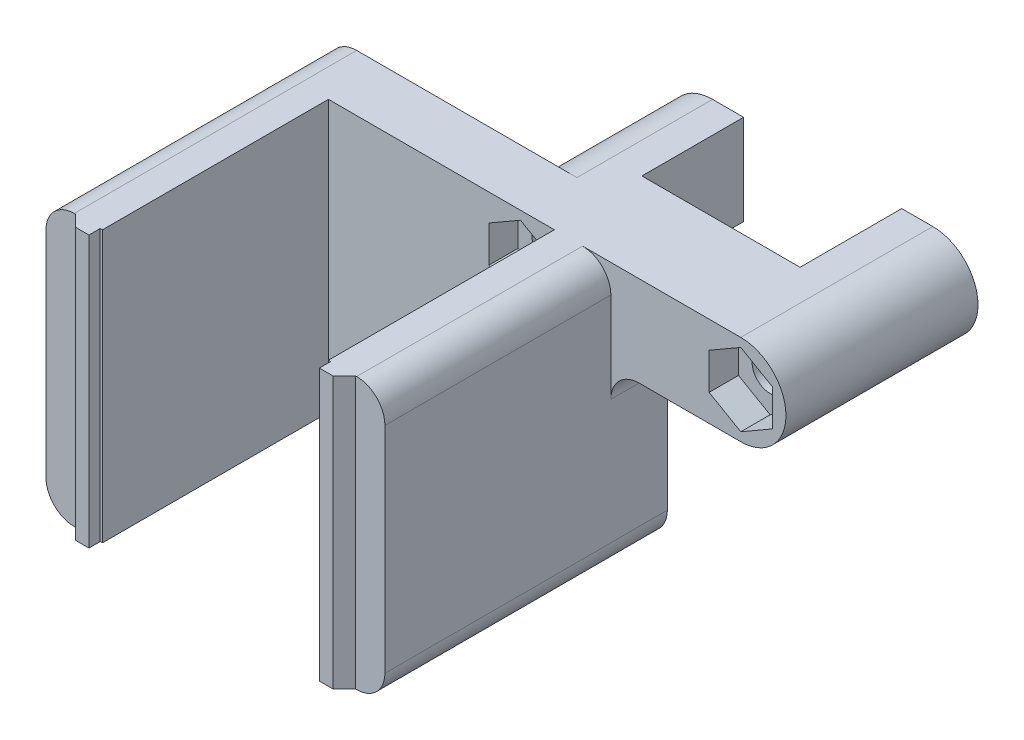
SolidWorks part; units mm, degrees
ref_plane "Спереди" through (0, 0, 0) normal (0, 0, 1) x (1, 0, 0)
ref_plane "Сверху" through (0, 0, 0) normal (0, 1, 0) x (1, 0, 0)
ref_plane "Справа" through (0, 0, 0) normal (1, 0, 0) x (0, 0, -1)
sketch "Эскиз1" plane through (0, 0, 0) normal (0, 0, 1) x (1, 0, 0)
  line L1 (0, 0) -> (30, 0)
  line L2 (0, 0) -> (0, -24)
  line L3 (0, -24) -> (30, -24)
  line L4 (30, 0) -> (30, -24)
  dimension "D1" = 24
  dimension "D2" = 30
extrude "Бобышка-Вытянуть1" add sketch "Эскиз1" along normal blind 5
sketch "Эскиз2" plane through (0, 0, 5) normal (0, 0, 1) x (1, 0, 0)
  line L1 (0, -24) -> (5, -24)
  line L2 (0, -24) -> (0, 0)
  line L3 (0, 0) -> (5, 0)
  line L4 (5, -24) -> (5, 0)
  line L5 (30, 0) -> (0, 0) construction
  line L7 (30, -24) -> (25, -24)
  line L8 (30, -24) -> (30, 0)
  line L9 (30, 0) -> (25, 0)
  line L10 (25, -24) -> (25, 0)
  dimension "D1" = 24
  dimension "D2" = 5
  dimension "D3" = 24
  dimension "D4" = 5
extrude "Бобышка-Вытянуть2" add sketch "Эскиз2" along normal blind 20
sketch "Эскиз3" plane through (0, 0, 0) normal (0, 1, 0) x (1, 0, 0)
  line L0 (25.2, -25) -> (25.2, -26)
  line L1 (30, -25) -> (25, -25) construction
  line L2 (25.2, -26) -> (26.4, -26)
  line L3 (26.4, -26) -> (27.4, -25)
  line L4 (27.4, -25) -> (25.2, -25)
  line L5 (25, -25) -> (25, -5) construction
  line L6 (4.8, -25) -> (4.8, -26)
  line L7 (5, -25) -> (0, -25) construction
  line L8 (4.8, -26) -> (3.6, -26)
  line L9 (3.6, -26) -> (2.6, -25)
  line L10 (2.6, -25) -> (4.8, -25)
  line L11 (5, -25) -> (5, -5) construction
  dimension "D1" = 45
  dimension "D2" = 1
  dimension "D3" = 1.2
  dimension "D4" = 0.2
  dimension "D5" = 45
  dimension "D6" = 0.2
  dimension "D7" = 1.2
  dimension "D8" = 1
extrude "Бобышка-Вытянуть3" add sketch "Эскиз3" against normal up to surface (24 mm away) up to face at (15, -24, 13.75)
sketch "Эскиз4" plane through (0, 0, 0) normal (0, 0, -1) x (-1, 0, 0)
  line L0 (0, -24) -> (-30, -24) construction
  line L1 (0, 0) -> (0, -24) construction
  circle A0 centre (-15, -14) radius 2.6
  dimension "D1" = 5.2
  dimension "D2" = 10
  dimension "D3" = 15
extrude "Вырез-Вытянуть1" cut sketch "Эскиз4" against normal through all
sketch "Эскиз5" plane through (0, 0, 0) normal (0, 0, -1) x (-1, 0, 0)
  line L0 (-22, 0) -> (-41.5, 0)
  line L1 (-41.5, -8) -> (-22, -8)
  line L2 (0, 0) -> (0, -24) construction
  line L3 (-30, 0) -> (0, 0) construction
  line L4 (-30, -24) -> (-30, 0) construction
  arc A0 (-22, -8) -> (-22, 0) centre (-22, -4) ccw
  arc A1 (-41.5, 0) -> (-41.5, -8) centre (-41.5, -4) ccw
  dimension "D1" = 8
  dimension "D2" = 8
  dimension "D3" = 19.5
  dimension "D4" = 41.5
  dimension "D5" = 11.5
  dimension "D6" = 22
extrude "Бобышка-Вытянуть4" add sketch "Эскиз5" along normal blind 12 and the other way up to surface (5 mm away) other way up to face at (17.6, -14, 5)
sketch "Эскиз6" plane through (0, 0, -12) normal (0, 0, -1) x (-1, 0, 0)
  line L1 (-24.75, 0) -> (-38.75, 0)
  line L2 (-24.75, 0) -> (-24.75, -8)
  line L3 (-24.75, -8) -> (-38.75, -8)
  line L4 (-38.75, 0) -> (-38.75, -8)
  line L6 (-22, 0) -> (-41.5, 0) construction
  line L7 (-41.5, -8) -> (-22, -8) construction
  point P8 (-31.75, 0)
  point P9 (-31.75, 0)
  dimension "D1" = 8
  dimension "D2" = 14
extrude "Вырез-Вытянуть2" cut sketch "Эскиз6" against normal blind 9
sketch "Эскиз7" plane through (0, 0, -12) normal (0, 0, -1) x (-1, 0, 0)
  circle A0 centre (-22, -4) radius 1.6
  circle A1 centre (-41.5, -4) radius 1.6
  dimension "D1" = 3.2
  dimension "D2" = 3.2
extrude "Вырез-Вытянуть3" cut sketch "Эскиз7" against normal through all
sketch "Эскиз8" plane through (0, 0, 5) normal (0, 0, 1) x (1, 0, 0)
  line L1 (41.5, -0.7668) -> (38.7, -2.3834)
  line L2 (38.7, -2.3834) -> (38.7, -5.6166)
  line L3 (38.7, -5.6166) -> (41.5, -7.2332)
  line L4 (41.5, -7.2332) -> (44.3, -5.6166)
  line L5 (44.3, -5.6166) -> (44.3, -2.3834)
  line L6 (44.3, -2.3834) -> (41.5, -0.7668)
  line L7 (22, -0.7668) -> (19.2, -2.3834)
  line L8 (19.2, -2.3834) -> (19.2, -5.6166)
  line L9 (19.2, -5.6166) -> (22, -7.2332)
  line L10 (22, -7.2332) -> (24.8, -5.6166)
  line L11 (24.8, -5.6166) -> (24.8, -2.3834)
  line L12 (24.8, -2.3834) -> (22, -0.7668)
  circle A0 centre (41.5, -4) radius 2.8 construction
  circle A1 centre (22, -4) radius 2.8 construction
  dimension "D1" = 5.6
  dimension "D2" = 5.6
extrude "Вырез-Вытянуть4" cut sketch "Эскиз8" against normal blind 2.6
sketch "Эскиз10" plane through (0, 0, 0) normal (0, 0, -1) x (-1, 0, 0)
  line L1 (-15, -18.7343) -> (-10.9, -16.3671)
  line L2 (-10.9, -16.3671) -> (-10.9, -11.6329)
  line L3 (-10.9, -11.6329) -> (-15, -9.2657)
  line L4 (-15, -9.2657) -> (-19.1, -11.6329)
  line L5 (-19.1, -11.6329) -> (-19.1, -16.3671)
  line L6 (-19.1, -16.3671) -> (-15, -18.7343)
  circle A0 centre (-15, -14) radius 4.1 construction
  circle A1 centre (-15, -14) radius 6
  dimension "D1" = 8.2
  dimension "D2" = 12
extrude "Бобышка-Вытянуть5" add sketch "Эскиз10" along normal blind 1
fillet "Скругление1" radius 2.5 4 edges at (30, -24, 12.5) (30, 0, 15) (0, -24, 12.5) (0, 0, 12.5)
fillet "Скругление2" radius 2.5 1 edges at (30, -8, 2.5)
chamfer "Фаска1" distance 1 angle 45 1 edges at (21, -14, 0)
